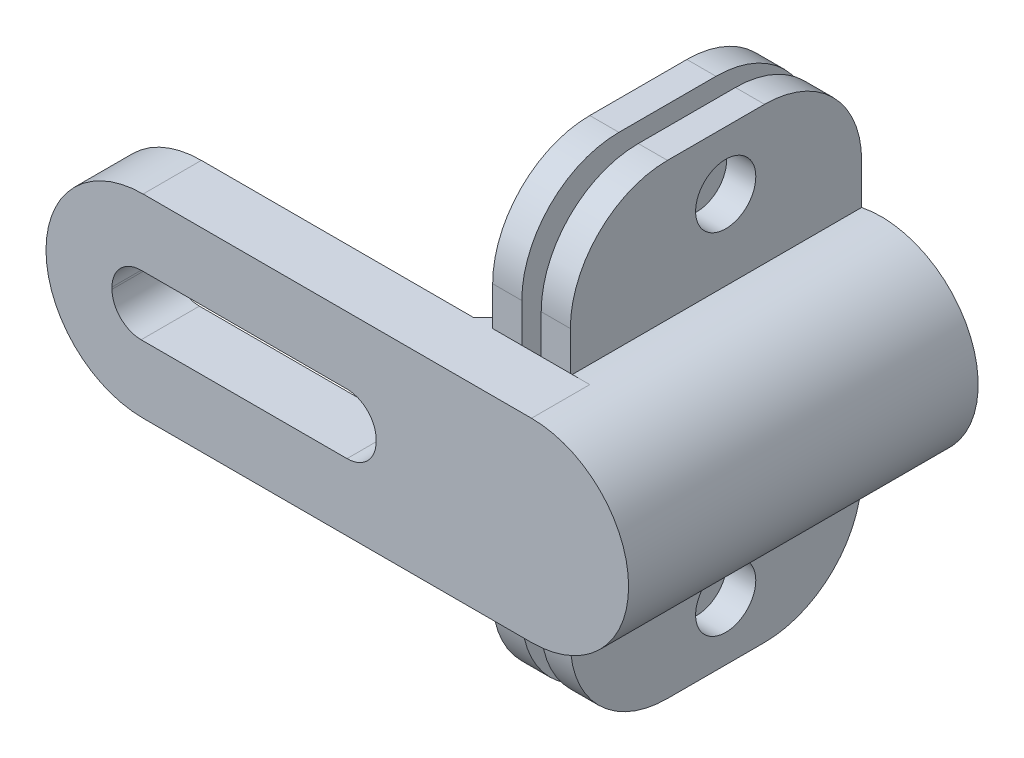
SolidWorks part; units mm, degrees
ref_plane "Płaszczyzna przednia" through (0, 0, 0) normal (0, 0, 1) x (1, 0, 0)
ref_plane "Płaszczyzna górna" through (0, 0, 0) normal (0, 1, 0) x (1, 0, 0)
ref_plane "Płaszczyzna prawa" through (0, 0, 0) normal (1, 0, 0) x (0, 0, -1)
sketch "Szkic1" plane through (0, 0, 0) normal (0, 0, 1) x (1, 0, 0)
  line L1 (0, 0) -> (30, 0)
  line L2 (0, 0) -> (0, 10)
  line L3 (0, 10) -> (30, 10)
  line L4 (30, 0) -> (30, 10)
  point P5 (0, 0)
extrude "Dodanie-wyciągnięcie1" add sketch "Szkic1" along normal blind 3
fillet "Zaokrąglenie1" radius 5 4 edges at (0, 10, 1.5) (0, 0, 1.5) (30, 10, 1.5) (30, 0, 1.5)
sketch "Szkic2" plane through (0, 0, 3) normal (0, 0, 1) x (1, 0, 0)
  line L1 (3.4, 6.55) -> (17, 6.55)
  line L2 (3.4, 6.55) -> (3.4, 3.45)
  line L3 (3.4, 3.45) -> (17, 3.45)
  line L4 (17, 6.55) -> (17, 3.45)
  point P4 (0, 0)
  point P5 (0, 0)
  point P6 (0, 0)
  point P7 (0, 0)
  point P8 (0, 0)
extrude "Wytnij-wyciągnięcie1" cut sketch "Szkic2" against normal up to next
fillet "Zaokrąglenie2" radius 1.5 4 edges at (3.4, 3.45, 1.5) (3.4, 6.55, 1.5) (17, 3.45, 1.5) (17, 6.55, 1.5)
sketch "Szkic3" plane through (0, 0, 0) normal (0, 0, -1) x (-1, 0, 0)
  circle A0 centre (-25, 5) radius 5
extrude "Dodanie-wyciągnięcie2" add sketch "Szkic3" along normal blind 15
sketch "Szkic5" plane through (0, 0, -15) normal (0, 0, -1) x (-1, 0, 0)
  line L1 (-20, -7) -> (-21.5, -7)
  line L2 (-20, -7) -> (-20, 17)
  line L3 (-20, 17) -> (-21.5, 17)
  line L4 (-21.5, -7) -> (-21.5, 17)
  line L5 (-22.5, -7) -> (-24, -7)
  line L6 (-22.5, -7) -> (-22.5, 17)
  line L7 (-22.5, 17) -> (-24, 17)
  line L8 (-24, -7) -> (-24, 17)
  point P8 (0, 0)
  point P9 (0, 0)
  point P10 (0, 0)
  point P11 (0, 0)
  point P12 (0, 0)
  point P13 (0, 0)
  point P14 (0, 0)
  point P15 (0, 0)
  point P16 (0, 0)
  point P17 (0, 0)
extrude "Dodanie-wyciągnięcie3" add sketch "Szkic5" against normal blind 15
sketch "Szkic4" plane through (0, 0, -15) normal (0, 0, -1) x (-1, 0, 0)
  circle A0 centre (-25, 5) radius 4.05
extrude "Wytnij-wyciągnięcie2" cut sketch "Szkic4" against normal blind 15
sketch "Szkic6" plane through (0, 0, -15) normal (0, 0, -1) x (-1, 0, 0)
  line L0 (-22.5, 9.3301) -> (-22.5, 17) construction
  line L1 (-22.5, 9.9451) -> (-21.5, 9.9451)
  line L2 (-22.5, 9.9451) -> (-22.5, -0.6863)
  line L3 (-22.5, -0.6863) -> (-21.5, -0.6863)
  line L4 (-21.5, 9.9451) -> (-21.5, -0.6863)
  line L5 (-21.5, 1.4293) -> (-21.5, -7) construction
extrude "Wytnij-wyciągnięcie3" cut sketch "Szkic6" against normal blind 15
sketch "Szkic7" plane through (24, 0, 0) normal (1, 0, 0) x (0, 0, -1)
  circle A0 centre (8, -4) radius 1.55
  circle A1 centre (8, 14) radius 1.55
  point P4 (0, 0)
  point P5 (0, 0)
extrude "Wytnij-wyciągnięcie4" cut sketch "Szkic7" against normal through all
fillet "Zaokrąglenie3" radius 5 8 edges at (20.75, 17, 0) (23.25, 17, 0) (23.25, 17, -15) (20.75, 17, -15) (23.25, -7, 0) (20.75, -7, 0) (23.25, -7, -15) (20.75, -7, -15)
chamfer "Sfazowanie1" distance 1 angle 45 1 edges at (20, 5, 0)
